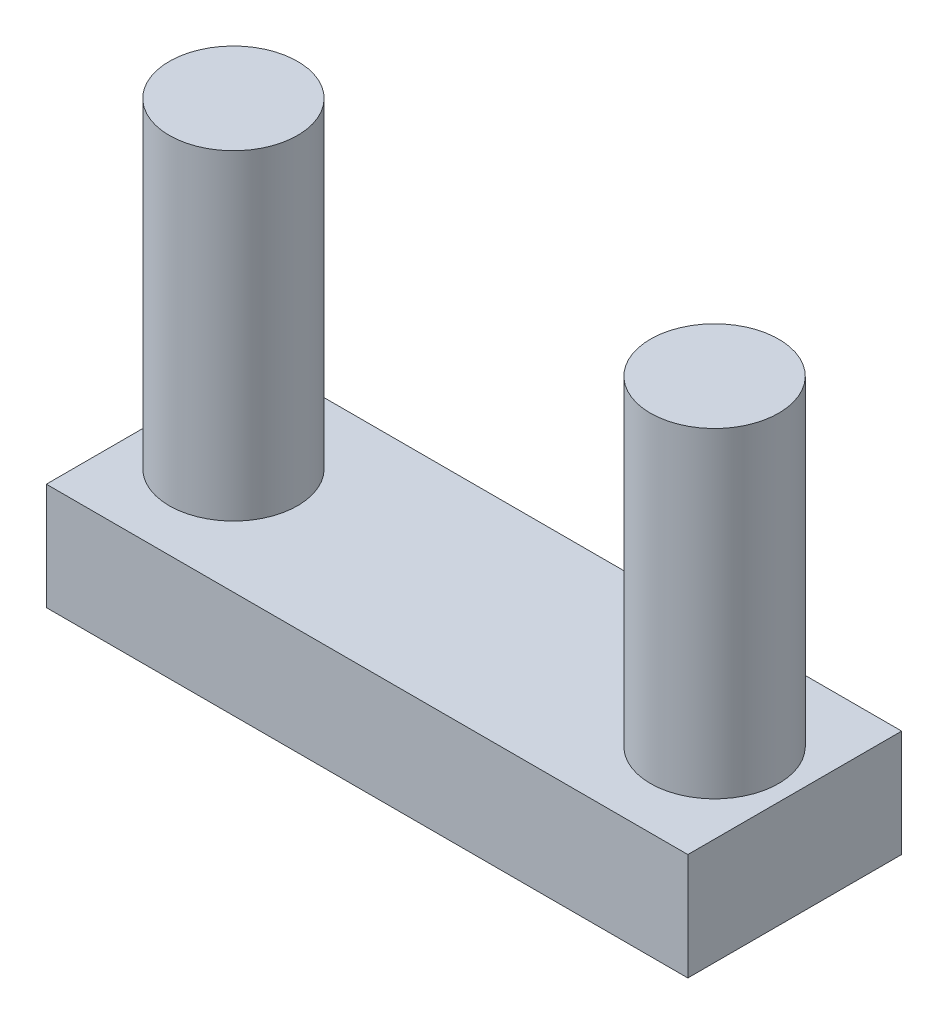
SolidWorks part; units mm, degrees
ref_plane "Front Plane" through (0, 0, 0) normal (0, 0, 1) x (1, 0, 0)
ref_plane "Top Plane" through (0, 0, 0) normal (0, 1, 0) x (1, 0, 0)
ref_plane "Right Plane" through (0, 0, 0) normal (1, 0, 0) x (0, 0, -1)
sketch "Sketch1" plane through (0, 0, 0) normal (0, 1, 0) x (1, 0, 0)
  line L0 (0, 0) -> (22.5, 0) construction
  line L2 (-3.75, 5) -> (26.25, 5)
  line L3 (-3.75, 5) -> (-3.75, -5)
  line L4 (-3.75, -5) -> (26.25, -5)
  line L5 (26.25, 5) -> (26.25, -5)
  circle A0 centre (0, 0) radius 3
  circle A1 centre (22.5, 0) radius 3
  dimension "D2" = 6
  dimension "D3" = 30
  dimension "D1" = 22.5
  dimension "D4" = 3.75
  dimension "D5" = 10
extrude "Boss-Extrude1" add sketch "Sketch1" along normal blind 5
extrude "Boss-Extrude2" add sketch "Sketch1<2>" along normal blind 20 contours A0 | A1 region at (0, 0, 0) region at (22.5, 0, 0)
sketch "Sketch1<2>" plane through (0, 0, 0) normal (0, 1, 0) x (1, 0, 0) same geometry as "Sketch1"
